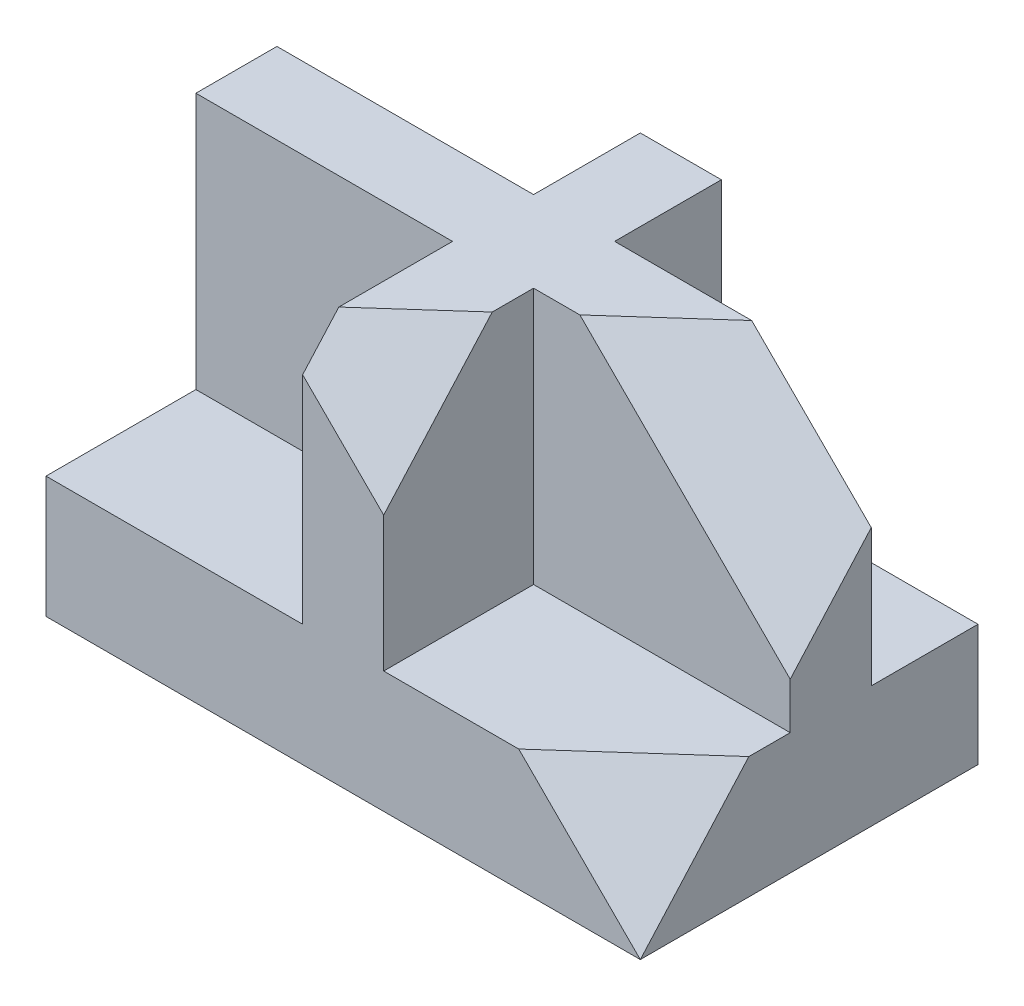
SolidWorks part; units mm, degrees
ref_plane "Front Plane" through (0, 0, 0) normal (0, 0, 1) x (1, 0, 0)
ref_plane "Top Plane" through (0, 0, 0) normal (0, 1, 0) x (1, 0, 0)
ref_plane "Right Plane" through (0, 0, 0) normal (1, 0, 0) x (0, 0, -1)
sketch "Sketch1" plane through (0, 0, 0) normal (0, 1, 0) x (1, 0, 0)
  line L1 (-41.1387, 25.6243) -> (46.8613, 25.6243)
  line L2 (-41.1387, 25.6243) -> (-41.1387, -24.3757)
  line L3 (-41.1387, -24.3757) -> (46.8613, -24.3757)
  line L4 (46.8613, 25.6243) -> (46.8613, -24.3757)
  dimension "D1" = 88
  dimension "D2" = 50
extrude "Boss-Extrude1" add sketch "Sketch1" along normal blind 18
sketch "Sketch2" plane through (0, 18, 0) normal (0, 1, 0) x (1, 0, 0)
  line L0 (-41.1387, 9.8182) -> (-3.1387, 9.8182)
  line L1 (-41.1387, 25.6243) -> (-41.1387, -24.3757) construction
  line L2 (-3.1387, 9.8182) -> (-3.1387, 25.6243)
  line L3 (46.8613, 25.6243) -> (-41.1387, 25.6243) construction
  line L4 (-3.1387, 25.6243) -> (8.8613, 25.6243)
  line L5 (8.8613, 25.6243) -> (8.8613, 9.8182)
  line L6 (8.8613, 9.8182) -> (46.8613, 9.8182)
  line L7 (46.8613, -24.3757) -> (46.8613, 25.6243) construction
  line L8 (46.8613, 9.8182) -> (46.8613, -2.1818)
  line L9 (46.8613, -2.1818) -> (8.8613, -2.1818)
  line L10 (8.8613, -2.1818) -> (8.8613, -24.3757)
  line L11 (-41.1387, -24.3757) -> (46.8613, -24.3757) construction
  line L12 (8.8613, -24.3757) -> (-3.1387, -24.3757)
  line L13 (-3.1387, -24.3757) -> (-3.1387, -2.1818)
  line L14 (-3.1387, -2.1818) -> (-41.1387, -2.1818)
  line L15 (-41.1387, -2.1818) -> (-41.1387, 9.8182)
  point P4 (0, 0)
  point P21 (0, 0)
  point P22 (0, 0)
  point P23 (0, 0)
  point P24 (0, 0)
  dimension "D1" = 38
  dimension "D2" = 38
  dimension "D3" = 12
  dimension "D4" = 12
  dimension "D5" = 12
  dimension "D6" = 12
extrude "Boss-Extrude2" add sketch "Sketch2" along normal blind 38
sketch "Sketch3" plane through (0, 56, 0) normal (0, 1, 0) x (1, 0, 0)
  line L1 (-41.1387, 25.6243) -> (46.8613, 25.6243) construction
  line L2 (-41.1387, 25.6243) -> (-41.1387, -24.3757) construction
  line L3 (-41.1387, -24.3757) -> (46.8613, -24.3757) construction
  line L4 (46.8613, 25.6243) -> (46.8613, -24.3757) construction
  line L5 (-41.1387, 25.6243) -> (46.8613, -24.3757) construction
  line L6 (-41.1387, -24.3757) -> (46.8613, 25.6243) construction
  point P0 (2.8613, 0.6243)
  point P6 (-41.1387, 25.6243)
sketch "Sketch4" plane through (0, 0, 24.3757) normal (0, 0, 1) x (1, 0, 0)
  line L0 (46.8613, 0) -> (-9.1387, 56) construction
  line L1 (-41.1387, 56) -> (46.8613, 56) construction
  line L2 (-41.1387, 0) -> (46.8613, 0) construction
  dimension "D1" = 45
ref_plane "Plane1" through (22.7883, 22.7883, 25.5228) normal (-0.5543, -0.5543, -0.6208) x (-0.8323, 0.3692, 0.4135)
sketch "Sketch5" plane through (22.7883, 22.7883, 25.5228) normal (-0.5543, -0.5543, -0.6208) x (-0.8323, 0.3692, 0.4135)
  line L0 (-28.9235, -16.2346) -> (38.3599, 25.5379)
  line L1 (38.3599, 25.5379) -> (-28.9235, 58.8387)
  line L2 (-28.9235, 58.8387) -> (-28.9235, -16.2346)
extrude "Cut-Extrude1" cut sketch "Sketch5" against normal blind 58
